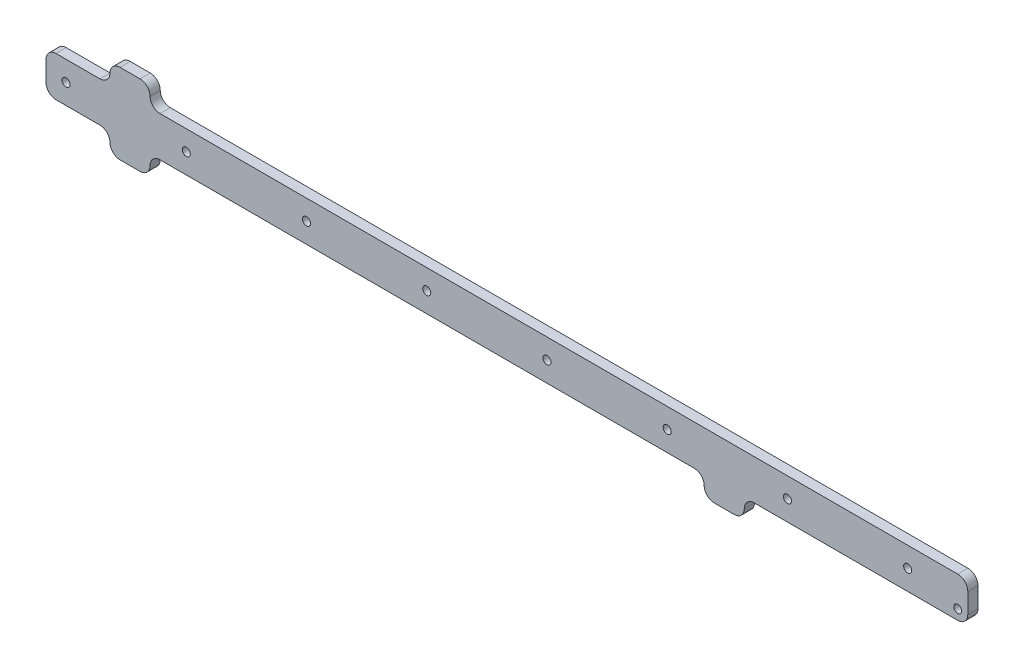
SolidWorks part; units mm, degrees
material "PC High Viscosity"
ref_plane "Front Plane" through (0, 0, 0) normal (0, 0, 1) x (1, 0, 0)
ref_plane "Top Plane" through (0, 0, 0) normal (0, 1, 0) x (1, 0, 0)
ref_plane "Right Plane" through (0, 0, 0) normal (1, 0, 0) x (0, 0, -1)
sketch "Sketch1" plane through (0, 0, 0) normal (0, 0, 1) x (1, 0, 0)
  line L0 (40.5308, 0) -> (40.5308, -12.7)
  line L1 (0, 0) -> (40.5308, 0)
  line L2 (0, 0) -> (0, 25.4)
  line L3 (0, 25.4) -> (40.5308, 25.4)
  line L4 (584.2, 0) -> (584.2, 25.4)
  line L5 (40.5308, 38.1) -> (65.9308, 38.1)
  line L6 (65.9308, 38.1) -> (65.9308, 25.4)
  line L7 (40.5308, 38.1) -> (40.5308, 25.4)
  line L8 (65.9308, 0) -> (65.9308, -12.7)
  line L9 (65.9308, -12.7) -> (40.5308, -12.7)
  line L11 (584.2, 10.0162) -> (577.85, 13.6823) construction
  line L12 (577.85, 13.6823) -> (571.5, 10.0162) construction
  line L13 (571.5, 10.0162) -> (571.5, 2.6838) construction
  line L14 (571.5, 2.6838) -> (577.85, -0.9823) construction
  line L15 (577.85, -0.9823) -> (584.2, 2.6838) construction
  line L16 (584.2, 2.6838) -> (584.2, 10.0162) construction
  line L19 (417.1409, 0) -> (417.1409, -12.7)
  line L20 (417.1409, -12.7) -> (442.5409, -12.7)
  line L21 (442.5409, -12.7) -> (442.5409, 0)
  line L22 (65.9308, 25.4) -> (584.2, 25.4)
  line L23 (65.9308, 0) -> (417.1409, 0)
  line L24 (442.5409, 0) -> (584.2, 0)
  circle A0 centre (577.85, 6.35) radius 2.4892
  circle A1 centre (577.85, 6.35) radius 6.35 construction
  point P24 (417.1409, -6.35)
  dimension "D5" = 4.9784
  dimension "D6" = 12.7
  dimension "D7" = 12.7
  dimension "D1" = 584.2
  dimension "D2" = 25.4
  dimension "D3" = 25.4
  dimension "D4" = 167.0591
  dimension "D8" = 40.5308
extrude "Boss-Extrude1" add sketch "Sketch1" along normal blind 6.477 contours L6 L5 L3 | L1 L4 L3 L2 A0 | L9 L8 L1 region at (284.8004, 12.3186, 0)
fillet "Fillet2" radius 6.35 16 edges at (65.9308, 38.1, 3.2385) (65.9308, -12.7, 3.2385) (40.5308, -12.7, 3.2385) (40.5308, 0, 3.2385) (0, 0, 3.2385) (40.5308, 38.1, 3.2385) (40.5308, 25.4, 3.2385) (0, 25.4, 3.2385) (442.5409, -12.7, 3.2385) (417.1409, -12.7, 3.2385) (417.1409, 0, 3.2385) (65.9308, 0, 3.2385) (584.2, 25.4, 3.2385) (584.2, 0, 3.2385) (442.5409, 0, 3.2385) (65.9308, 25.4, 3.2385)
sketch "Sketch2" plane through (0, 0, 6.477) normal (0, 0, 1) x (1, 0, 0)
  line L0 (6.35, 25.4) -> (34.1808, 25.4) construction
  line L1 (584.2, 19.05) -> (584.2, 6.35) construction
  circle A0 centre (546.1, 12.7) radius 2.0193
  dimension "D1" = 4.0386
  dimension "D2" = 12.7
  dimension "D3" = 38.1
hole_wizard "CSK for #10 Flat Head Machine Screw (100)1" positions "Sketch4" profile "Sketch5" countersink size "#10" standard "ANSI Inch" end condition through all
sketch "Sketch4" plane through (0, 0, 6.477) normal (0, 0, 1) x (1, 0, 0)
  line L0 (584.2, 12.7) -> (0, 12.7) construction
  line L1 (584.2, 19.05) -> (584.2, 6.35) construction
  line L2 (0, 6.35) -> (0, 19.05) construction
  line L3 (6.35, 25.4) -> (34.1808, 25.4) construction
  point P11 (546.1, 12.7)
  dimension "D1" = 12.7
  dimension "D2" = 38.1
sketch "Sketch5" plane through (546.1, 12.7, 6.477) normal (1, 0, 0) x (0, -1, 0)
  line L0 (0, 0) -> (0, 6.477)
  line L1 (0, 6.477) -> (2.5527, 6.477)
  line L2 (2.5527, 6.477) -> (2.5527, 1.9608)
  line L3 (2.5527, 1.9608) -> (4.8895, 0)
  line L5 (4.8895, 0) -> (0, 0)
  line L6 (-2.5527, 1.9608) -> (-4.8895, 0) construction
  line L11 (0, -6.35) -> (0, 107.95) construction
  dimension "Thru Hole Dia." = 5.1054
  dimension "Thru Hole Depth" = 6.477
  dimension "Near C'Sink Dia." = 9.779
  dimension "Near C'Sink Angle" = 100
pattern_linear "LPattern1" count 8 spacing 76.2 along (-1, 0, 0) of "CSK for #10 Flat Head Machine Screw (100)1"
mirror "Mirror2" about plane through (0, 0, 0) normal (0, 0, 1) of bodies 108
delete or keep bodies "Body-Delete/Keep 1" type delete bodies bodies 108
